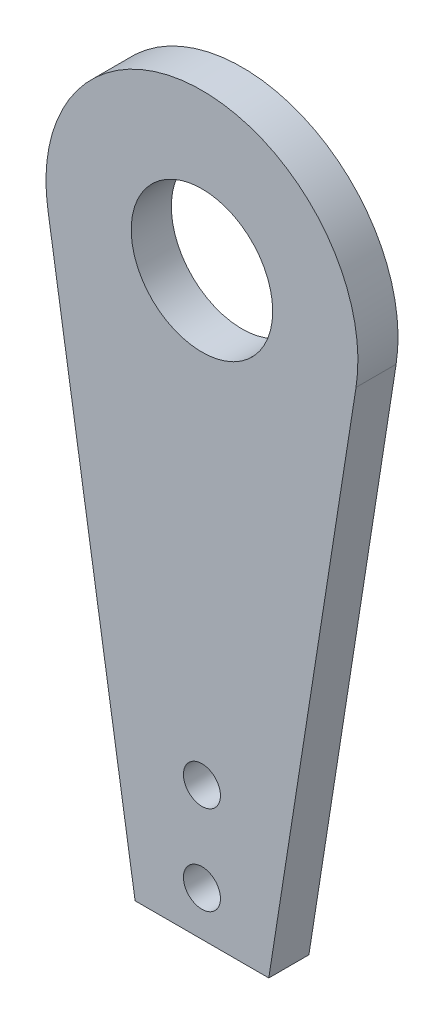
SolidWorks part; units mm, degrees
ref_plane "Front Plane" through (0, 0, 0) normal (0, 0, 1) x (1, 0, 0)
ref_plane "Top Plane" through (0, 0, 0) normal (0, 1, 0) x (1, 0, 0)
ref_plane "Right Plane" through (0, 0, 0) normal (1, 0, 0) x (0, 0, -1)
ref_axis "X Axis" through (-88.99, 0, 0) along (1, 0, 0)
ref_axis "Y Axiz" through (0, 0, 55) along (0, 0, -1)
ref_axis "Z Axis" through (0, 55, 0) along (0, -1, 0)
sketch "Sketch1" plane through (0, 0, 0) normal (0, 0, 1) x (1, 0, 0)
  line L0 (-7.5, -5) -> (7.5, -5)
  line L1 (-7.5, -5) -> (-17.2878, 57.2832)
  line L2 (0, -5) -> (0, 0) construction
  line L4 (17.2878, 57.2832) -> (7.5, -5)
  line L5 (0, 0) -> (0, 60) construction
  circle A0 centre (0, 0) radius 2.075
  circle A2 centre (0, 60) radius 7.9375
  arc A3 (17.2878, 57.2832) -> (-17.2878, 57.2832) centre (0, 60) ccw
  circle A4 centre (0, 10) radius 2.075
  dimension "D1" = 4.15
  dimension "D3" = 5
  dimension "D4" = 15.875
  dimension "D5" = 35
  dimension "D2" = 10
  dimension "D6" = 60
  dimension "D7" = 15
extrude "Boss-Extrude2" add sketch "Sketch1" along normal blind 4.5
